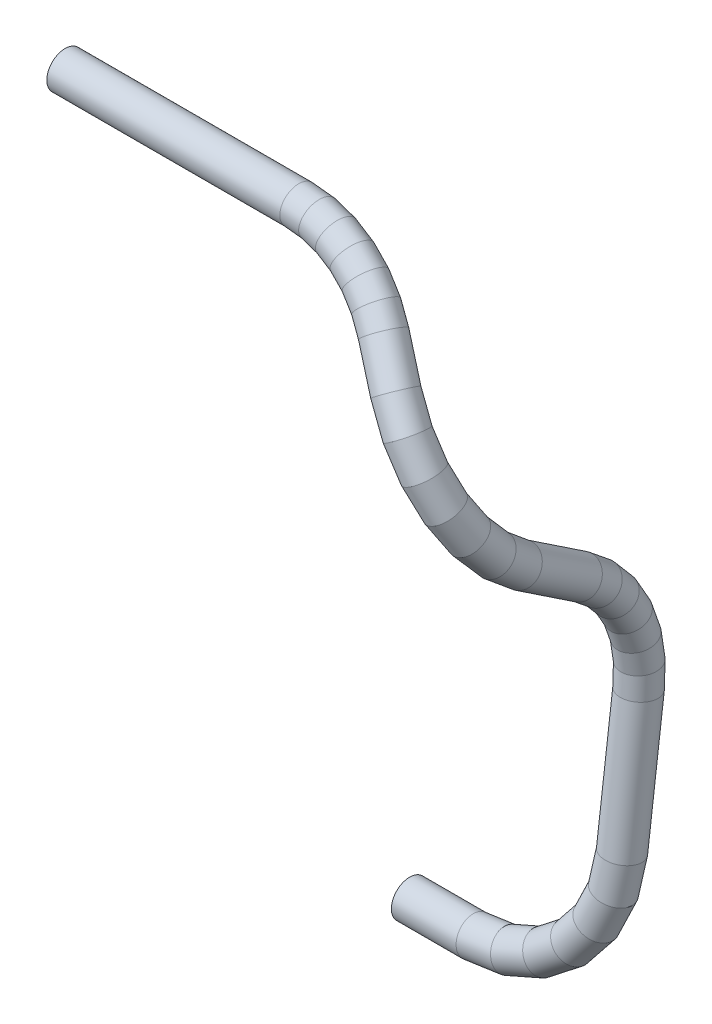
SolidWorks part; units mm, degrees
ref_plane "Front Plane" through (0, 0, 0) normal (0, 0, 1) x (1, 0, 0)
ref_plane "Top Plane" through (0, 0, 0) normal (0, 1, 0) x (1, 0, 0)
ref_plane "Right Plane" through (0, 0, 0) normal (1, 0, 0) x (0, 0, -1)
sketch3d "Path"
  line L0 (-571, 108.3711, -44.8888) -> (-539.0671, 108.3711, -44.8888)
  line L1 (-539.0671, 108.3711, -44.8888) -> (-536.2786, 108.1703, -44.8056)
  line L2 (-536.2786, 108.1703, -44.8056) -> (-533.5575, 107.5729, -44.5581)
  line L3 (-533.5575, 107.5729, -44.5581) -> (-530.9693, 106.5932, -44.1524)
  line L4 (-530.9693, 106.5932, -44.1524) -> (-528.5767, 105.2549, -43.598)
  line L5 (-528.5767, 105.2549, -43.598) -> (-526.4374, 103.5904, -42.9086)
  line L6 (-526.4374, 103.5904, -42.9086) -> (-524.603, 101.6398, -42.1006)
  line L7 (-524.603, 101.6398, -42.1006) -> (-521.1476, 97.33, -40.3154)
  line L8 (-521.1476, 97.33, -40.3154) -> (-518.694, 93.9901, -39.4663)
  line L9 (-518.694, 93.9901, -39.4663) -> (-516.4698, 90.3926, -39.5497)
  line L10 (-516.4698, 90.3926, -39.5497) -> (-514.598, 86.7362, -40.5608)
  line L11 (-514.598, 86.7362, -40.5608) -> (-513.1818, 83.2228, -42.444)
  line L12 (-513.1818, 83.2228, -42.444) -> (-512.2996, 80.0465, -45.0951)
  line L13 (-512.2996, 80.0465, -45.0951) -> (-512, 77.3827, -48.3678)
  line L14 (-512, 77.3827, -48.3678) -> (-512, 71.9311, -56.5267)
  line L15 (-512, 71.9311, -56.5267) -> (-512, 69.8453, -59.0997)
  line L16 (-512, 69.8453, -59.0997) -> (-512, 67.3234, -61.247)
  line L17 (-512, 67.3234, -61.247) -> (-512, 64.4507, -62.8958)
  line L18 (-512, 64.4507, -62.8958) -> (-512, 61.3245, -63.9904)
  line L19 (-512, 61.3245, -63.9904) -> (-512, 58.0507, -64.4936)
  line L20 (-512, 58.0507, -64.4936) -> (-512, 54.7401, -64.3884)
  line L21 (-512, 54.7401, -64.3884) -> (-512, 36.562, -62.1245)
  line L22 (-512, 36.562, -62.1245) -> (-512.6133, 31.939, -61.5488)
  line L23 (-512.6133, 31.939, -61.5488) -> (-514.4115, 27.631, -61.0123)
  line L24 (-514.4115, 27.631, -61.0123) -> (-517.2721, 23.9317, -60.5515)
  line L25 (-517.2721, 23.9317, -60.5515) -> (-521, 21.0931, -60.198)
  line L26 (-521, 21.0931, -60.198) -> (-525.3413, 19.3086, -59.9758)
  line L27 (-525.3413, 19.3086, -59.9758) -> (-530, 18.7, -59.9)
  line L28 (-530, 18.7, -59.9) -> (-538.85, 18.7, -59.9)
ref_plane "Start Plane" through (-571, 0, 0) normal (1, 0, 0) x (0, 0, -1)
sketch "Profile" plane through (-571, 0, 0) normal (1, 0, 0) x (0, 0, -1)
  circle A0 centre (44.8888, 108.3711) radius 2.5
  circle A1 centre (44.8888, 108.3711) radius 1
sweep "Tube" add profiles "Profile" path "Path"
ref_axis "Engine Axis" through (-506.425, 0, 0) along (-1, 0, 0)
